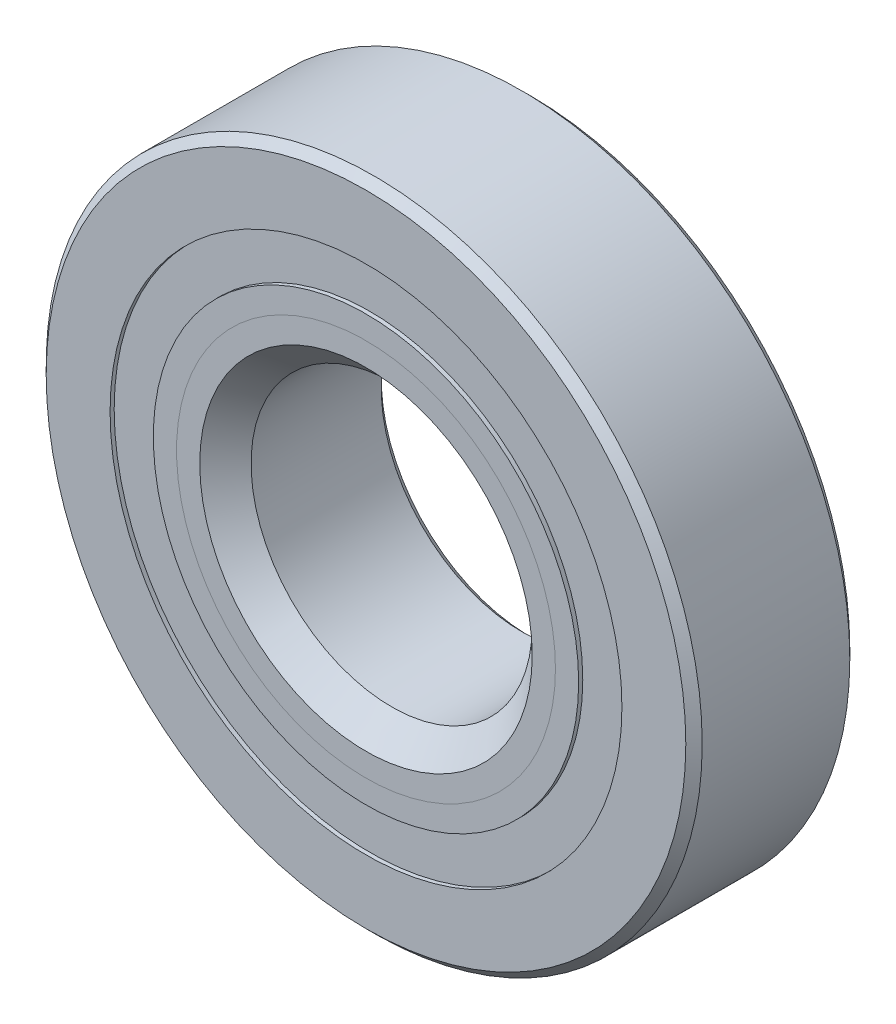
SolidWorks part; units mm, degrees
material "Alloy Steel"
ref_plane "Front Plane" through (0, 0, 0) normal (0, 0, 1) x (1, 0, 0)
ref_plane "Top Plane" through (0, 0, 0) normal (0, 1, 0) x (1, 0, 0)
ref_plane "Right Plane" through (0, 0, 0) normal (1, 0, 0) x (0, 0, -1)
sketch "Sketch1" plane through (0, 0, 0) normal (1, 0, 0) x (0, 0, -1)
  line L0 (-2.7781, 0) -> (2.7781, 0) construction
  line L1 (0, 11.1125) -> (0, -11.1125) construction
  line L2 (2.5003, 11.1125) -> (-2.5003, 11.1125)
  line L3 (-2.5003, 11.1125) -> (-2.7781, 10.8347)
  line L4 (-2.7781, 10.8347) -> (-2.7781, 8.6702)
  line L5 (-2.7781, 8.6702) -> (-1.2347, 8.6702)
  line L6 (2.7781, 8.6702) -> (1.2347, 8.6702)
  line L7 (2.7781, 10.8347) -> (2.7781, 8.6702)
  line L8 (2.5003, 11.1125) -> (2.7781, 10.8347)
  line L9 (0, 11.1125) -> (0, 7.9375) construction
  line L10 (0, 7.9375) -> (0, 4.7625) construction
  arc A0 (-1.2347, 8.6702) -> (1.2347, 8.6702) centre (0, 7.9375) cw
  point P14 (0, 4.7625)
  dimension "Width" = 5.5562
  dimension "OD" = 22.225
  dimension "D1" = 45
  dimension "D2" = 0.2778
  dimension "D3" = 2.4694
  dimension "D4" = 0.7327
revolve "Revolve1" add sketch "Sketch1" angle 360 about L0
sketch "Sketch2" plane through (0, 0, 0) normal (1, 0, 0) x (0, 0, -1)
  line L0 (-2.7781, 7.2048) -> (-1.2347, 7.2048)
  line L1 (-2.7781, 10.8347) -> (-2.7781, -10.8347) construction
  line L2 (-2.7781, 7.2048) -> (-2.7781, 6.4185)
  line L3 (-2.7781, 6.4185) -> (-1.9918, 5.6321)
  line L4 (-1.9918, 5.6321) -> (0, 5.6321)
  line L5 (0, 11.1125) -> (0, -11.1125) construction
  line L6 (0, 5.6321) -> (0, 6.5018)
  line L7 (0, 6.5018) -> (0, 4.7625) construction
  line L8 (-2.7781, 7.2048) -> (-2.7781, 5.6321) construction
  line L9 (-2.7781, 5.6321) -> (-1.9918, 5.6321) construction
  arc A0 (-1.2347, 7.2048) -> (0, 6.5018) centre (0, 7.9375) ccw
  arc A1 (1.2347, 8.6702) -> (-1.2347, 8.6702) centre (0, 7.9375) ccw construction
  circle A2 centre (0, 7.9375) radius 1.4357 construction
  dimension "D1" = 45
revolve "Revolve2" add sketch "Sketch2" angle 360 about L0
sketch "Sketch3" plane through (0, 0, 0) normal (1, 0, 0) x (0, 0, -1)
  line L0 (-2.7781, 6.4185) -> (-1.9918, 5.6321)
  line L1 (-1.9918, 5.6321) -> (0, 5.6321)
  line L2 (0, 5.6321) -> (0, 6.5018)
  line L3 (-2.7781, 6.4185) -> (-2.7781, 5.6321)
  line L4 (-2.7781, 7.2048) -> (-2.7781, 5.6321) construction
  line L5 (-2.7781, 5.6321) -> (-1.9085, 4.7625)
  line L6 (-1.9085, 4.7625) -> (2.5003, 4.7625)
  line L7 (2.5003, 11.1125) -> (2.5003, -11.1125) construction
  line L8 (2.5003, 4.7625) -> (2.7781, 5.0403)
  line L9 (2.7781, -10.8347) -> (2.7781, 10.8347) construction
  line L10 (2.7781, 5.0403) -> (2.7781, 7.2048)
  line L11 (2.7781, 7.2048) -> (1.2347, 7.2048)
  line L13 (2.5003, 11.1125) -> (2.7781, 10.8347) construction
  circle A0 centre (0, 7.9375) radius 1.4357 construction
  arc A1 (1.2347, 7.2048) -> (0, 6.5018) centre (0, 7.9375) cw
revolve "Revolve3" add sketch "Sketch3" angle 360 about L0
sketch "Sketch4" plane through (0, 0, 0) normal (1, 0, 0) x (0, 0, -1)
  line L0 (-1.4357, 7.9375) -> (1.4357, 7.9375)
  circle A1 centre (0, 7.9375) radius 1.4357 construction
  arc A2 (-1.4357, 7.9375) -> (1.4357, 7.9375) centre (0, 7.9375) cw
  arc A3 (1.2347, 8.6702) -> (-1.2347, 8.6702) centre (0, 7.9375) ccw construction
revolve "Revolve4" add sketch "Sketch4" angle 360 about L0
ref_axis "Axis1" through (0, 0, -2.7781) along (0, 0, 1)
pattern_circular "CirPattern1" count 12 every 30 about axis through (0, 0, -2.7781) along (0, 0, 1) of bodies 104
sketch "Sketch5" plane through (0, 0, 0) normal (1, 0, 0) x (0, 0, -1)
  line L0 (-2.6392, 8.6702) -> (-2.6392, 10.9736) construction
  line L1 (-2.6392, 8.6702) -> (-1.4357, 8.6702)
  line L2 (-2.6392, 8.6702) -> (-2.6392, 7.2048)
  line L3 (-2.6392, 7.2048) -> (-1.4357, 7.2048)
  line L4 (-1.4357, 8.6702) -> (-1.4357, 7.2048)
  line L5 (1.4357, 8.6702) -> (2.6392, 8.6702)
  line L6 (1.4357, 8.6702) -> (1.4357, 7.2048)
  line L7 (1.4357, 7.2048) -> (2.6392, 7.2048)
  line L8 (2.6392, 8.6702) -> (2.6392, 7.2048)
  line L9 (-2.5003, 11.1125) -> (-2.7781, 10.8347) construction
  line L10 (-2.7781, 8.6702) -> (-1.2347, 8.6702) construction
  line L11 (-2.7781, 7.2048) -> (-1.2347, 7.2048) construction
  circle A0 centre (0, 7.9375) radius 1.4357 construction
revolve "Revolve5" add sketch "Sketch5" angle 360 about L0
equation "\"D2@Sketch1\" = \"Width@Sketch1\"*.05"
equation "\"D3@Sketch1\" = \"Width@Sketch1\"/2.25"
equation "\"D4@Sketch1\" = (((\"OD@Sketch1\"-\"Width@Sketch1\")/2)/3.25)/3.5"
equation "\"D2@CirPattern1\" = 360/\"Balls@CirPattern1\""
